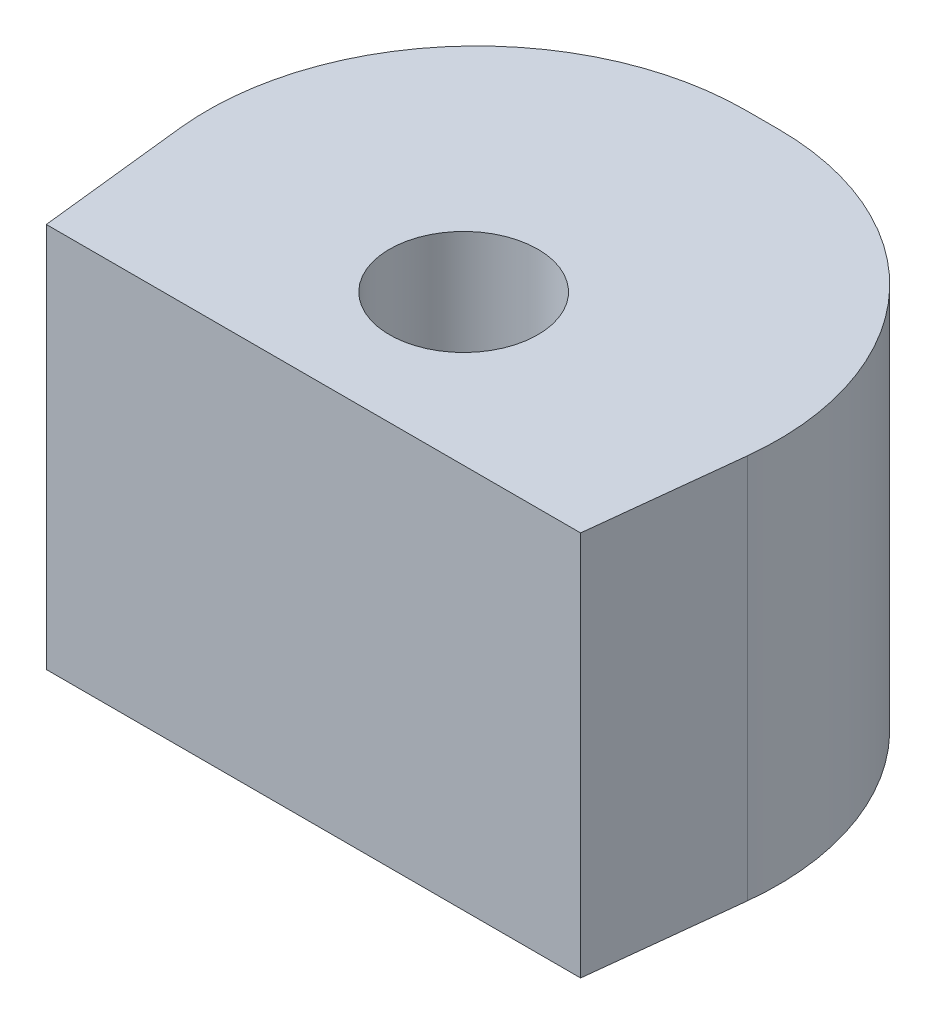
SolidWorks part; units mm, degrees
ref_plane "Front Plane" through (0, 0, 0) normal (0, 0, 1) x (1, 0, 0)
ref_plane "Top Plane" through (0, 0, 0) normal (0, 1, 0) x (1, 0, 0)
ref_plane "Right Plane" through (0, 0, 0) normal (1, 0, 0) x (0, 0, -1)
sketch "Sketch1" plane through (0, 0, 0) normal (0, 1, 0) x (1, 0, 0)
  line L0 (1.1081, 1.7265) -> (-45.0799, 1.7265) construction
  line L1 (-45.0799, 1.7265) -> (-45.0799, -11.2275) construction
  line L2 (-45.0799, -11.2275) -> (43.7517, -11.2275) construction
  line L3 (1.1081, 103.3269) -> (1.1081, -99.8738) construction
  line L4 (-45.0799, -11.2275) -> (-45.0799, -20.7525) construction
  line L5 (-28.2049, 1.7265) -> (-28.2049, -3.6075) construction
  line L6 (-9.9553, -3.6075) -> (-6.7697, -3.6075)
  line L7 (-28.2049, -3.6075) -> (-9.9553, -3.6075) construction
  line L8 (-6.7697, -3.6075) -> (1.1081, -3.6075) construction
  line L9 (8.9859, -3.6075) -> (12.1715, -3.6075)
  line L10 (12.1715, -3.6075) -> (18.1346, -3.6075) construction
  line L11 (12.1715, -3.6075) -> (18.1346, -3.6075) construction
  line L12 (18.1346, -3.6075) -> (29.3788, -3.6075) construction
  line L13 (1.1081, -3.6075) -> (8.9859, -3.6075) construction
  line L14 (-6.7697, -3.6075) -> (8.9859, -3.6075)
  circle A0 centre (1.1081, -11.3265) radius 1.9844 construction
  circle A1 centre (1.1081, -11.3265) radius 1.9844
  spline S0 degree 3 poles (1.1081, -99.8738) (4.5273, -73.5318) (7.9866, -47.1872) (10.6029, -20.7525) knots 0 0 0 0 0.38497 0.38497 0.38497 0.38497
  spline S3 degree 3 poles (1.1081, -99.8738) (-2.3112, -73.5318) (-5.7704, -47.1872) (-8.3867, -20.7525) knots 0 0 0 0 0.38497 0.38497 0.38497 0.38497
  spline S4 degree 3 poles (10.6029, -20.7525) (11.1, -15.7302) (11.6306, -10.016) (12.114, -4.2968) (12.1715, -3.6075) knots 0.38497 0.38497 0.38497 0.38497 0.458109 0.468132 0.468132 0.468132 0.468132
  spline S5 degree 3 poles (-8.3867, -20.7525) (-8.8838, -15.7302) (-9.4144, -10.016) (-9.8978, -4.2968) (-9.9553, -3.6075) knots 0.38497 0.38497 0.38497 0.38497 0.458109 0.468132 0.468132 0.468132 0.468132
  spline S8 degree 3 poles (12.1715, -3.6075) (12.8364, 4.367) (14.1908, 23.6726) (14.0058, 48.0803) (13.0188, 67.5796) (11.3266, 78.9472) (9.5869, 86.9693) (8.1237, 93.6397) (6.4505, 97.563) (4.8164, 101.3994) (2.3437, 102.5279) (1.1081, 103.3269) knots 0.468132 0.468132 0.468132 0.468132 0.584075 0.748482 0.821537 0.866809 0.914778 0.94069 0.965303 0.976863 1 1 1 1 construction
  spline S9 degree 3 poles (1.1081, 99.6196) (1.2739, 99.518) (1.6209, 99.2976) (2.0134, 99.0137) (2.3095, 98.7539) (2.4667, 98.5788) (2.6076, 98.3713) (2.8163, 97.9774) (3.0534, 97.4394) (3.4327, 96.5453) (3.8774, 95.496) (4.541, 93.8448) (5.2023, 91.9048) (5.8236, 89.3366) (6.4213, 86.5662) (7.0145, 83.8293) (7.767, 80.1951) (8.6007, 75.6781) (9.6391, 68.4081) (10.3034, 59.2354) (10.6788, 47.9926) (10.8555, 36.7918) (10.7415, 25.5951) (10.3009, 14.4244) (9.6564, 4.6878) (9.1767, -1.3266) (8.9859, -3.6075) knots 0.118744 0.118744 0.118744 0.118744 0.122149 0.125554 0.12896 0.132365 0.13577 0.139175 0.142581 0.145986 0.152796 0.159607 0.173228 0.186849 0.20047 0.214091 0.227711 0.254953 0.282195 0.336679 0.391163 0.445646 0.50013 0.554614 0.609098 0.642376 0.642376 0.642376 0.642376 construction
  spline S10 degree 3 poles (-7.1984, 1.7265) (-7.237, 2.2289) (-7.5577, 6.4638) (-8.0847, 14.4244) (-8.5253, 25.5951) (-8.6393, 36.7918) (-8.4626, 47.9926) (-8.0872, 59.2354) (-7.4229, 68.4081) (-6.3845, 75.6781) (-5.5508, 80.1951) (-4.7983, 83.8293) (-4.2051, 86.5662) (-3.6074, 89.3366) (-2.9861, 91.9048) (-2.3248, 93.8448) (-1.6612, 95.496) (-1.2165, 96.5453) (-0.8372, 97.4394) (-0.6001, 97.9774) (-0.3914, 98.3713) (-0.2505, 98.5788) (-0.0933, 98.7539) (0.2028, 99.0137) (0.5953, 99.2976) (0.9423, 99.518) (1.1081, 99.6196) knots 0.492798 0.492798 0.492798 0.492798 0.50013 0.554614 0.609098 0.663581 0.718065 0.772549 0.827033 0.854275 0.881516 0.895137 0.908758 0.922379 0.936 0.949621 0.956432 0.963242 0.966647 0.970053 0.973458 0.976863 0.980268 0.983674 0.987079 0.990484 0.990484 0.990484 0.990484 construction
  spline S11 degree 3 poles (-10.3826, 1.7265) (-10.8572, 7.9268) (-11.9611, 25.4575) (-11.7896, 48.0803) (-10.8026, 67.5796) (-9.1104, 78.9472) (-7.3707, 86.9693) (-5.9075, 93.6397) (-4.2343, 97.563) (-2.6002, 101.3994) (-0.1276, 102.5279) (1.1081, 103.3269) knots 0.493976 0.493976 0.493976 0.493976 0.584075 0.748482 0.821537 0.866809 0.914778 0.94069 0.965303 0.976863 1 1 1 1 construction
  spline S12 degree 3 poles (-9.9553, -3.6075) (-10.1035, -1.8299) (-10.2465, -0.0519) (-10.3826, 1.7265) knots 0.468132 0.468132 0.468132 0.468132 0.493976 0.493976 0.493976 0.493976 construction
  spline S13 degree 3 poles (-6.7697, -3.6075) (-6.9185, -1.8292) (-7.0618, -0.0511) (-7.1984, 1.7265) knots 0.466852 0.466852 0.466852 0.466852 0.492798 0.492798 0.492798 0.492798 construction
  dimension "D4" = 3.9688
  dimension "D1" = 12.954
  dimension "D2" = 9.525
  dimension "D3" = 5.334
extrude "Boss-Extrude1" add sketch "Sketch1" along normal blind 169.8727
sketch "Sketch2" plane through (0, 169.8727, 0) normal (0, 1, 0) x (1, 0, 0)
  line L1 (-9.9553, -3.6075) -> (25.8085, -3.6075)
  line L2 (-9.9553, -3.6075) -> (-9.9553, -26.3125)
  line L3 (-9.9553, -26.3125) -> (25.8085, -26.3125)
  line L4 (25.8085, -3.6075) -> (25.8085, -26.3125)
  circle A0 centre (1.1081, -11.3265) radius 1.9844 construction
  dimension "D1" = 14.986
extrude "Cut-Extrude1" cut sketch "Sketch2" against normal blind 23.0581
extrude "Cut-Extrude2" cut sketch "Sketch2<2>" along normal blind 23.0581 from surface starting at face at (-1.1046, 0, 29.7187)
sketch "Sketch2<2>" plane through (0, 169.8727, 0) normal (0, 1, 0) x (1, 0, 0) same geometry as "Sketch2"
fillet "Fillet1" radius 7.62 6 edges at (-7.8242, 11.5291, 26.3125) (10.0403, 11.5291, 26.3125) (12.1715, 84.9363, 3.6075) (-7.8242, 158.3436, 26.3125) (10.0403, 158.3436, 26.3125)
sketch "Sketch6" plane through (0, 0, 0) normal (0, -1, 0) x (1, 0, 0)
  line L0 (1.1081, 3.6075) -> (1.1081, 99.8738) construction
  line L1 (-1.6395, 3.6075) -> (3.8557, 3.6075) construction
  line L2 (-6.9254, 34.7606) -> (9.1416, 34.7606) construction
  circle A0 centre (1.1081, 71.9338) radius 2.1
  circle A1 centre (1.1081, 34.7606) radius 2.1
  dimension "D1" = 4.2
  dimension "D2" = 27.94
extrude "Cut-Extrude3" cut sketch "Sketch6" against normal through all both and the other way through all
sketch "Sketch7" plane through (0, 0, 0) normal (1, 0, 0) x (0, 0, -1)
  line L0 (-3.6075, 146.8145) -> (-3.6075, 23.0581) construction
  line L1 (-99.8738, 0) -> (-3.6075, 0)
  line L2 (-99.8738, 0) -> (-99.8738, 154.1951)
  line L3 (-99.8738, 154.1951) -> (-3.6075, 154.1951)
  line L4 (-3.6075, 0) -> (-3.6075, 154.1951)
  line L6 (-99.8738, 169.8727) -> (-3.6075, 169.8727)
  line L7 (-99.8738, 169.8727) -> (-99.8738, 165.1069)
  line L8 (-99.8738, 165.1069) -> (-3.6075, 165.1069)
  line L9 (-3.6075, 169.8727) -> (-3.6075, 165.1069)
  dimension "D2" = 10.9118
extrude "Cut-Extrude4" cut sketch "Sketch7" against normal through all both and the other way through all
sketch "Sketch8" plane through (0, 154.1951, 0) normal (0, -1, 0) x (1, 0, 0)
  line L1 (-35.7382, 103.9976) -> (19.5961, 103.9976)
  line L2 (-35.7382, 103.9976) -> (-35.7382, 39.0125)
  line L3 (-35.7382, 39.0125) -> (19.5961, 39.0125)
  line L4 (19.5961, 103.9976) -> (19.5961, 39.0125)
  dimension "D1" = 12.7
extrude "Cut-Extrude5" cut sketch "Sketch8" against normal through all both
